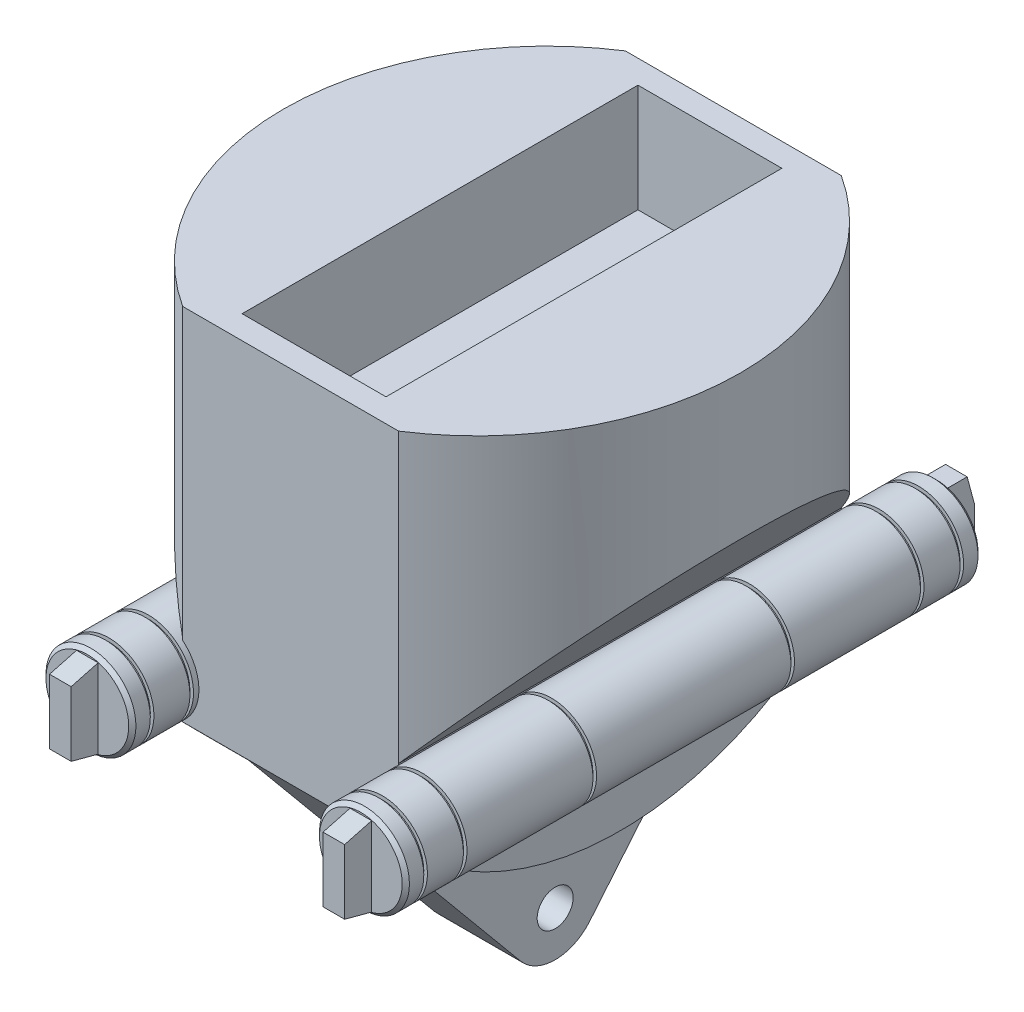
SolidWorks part; units mm, degrees
ref_plane "Front Plane" through (0, 0, 0) normal (0, 0, 1) x (1, 0, 0)
ref_plane "Top Plane" through (0, 0, 0) normal (0, 1, 0) x (1, 0, 0)
ref_plane "Right Plane" through (0, 0, 0) normal (1, 0, 0) x (0, 0, -1)
sketch "Sketch1" plane through (0, 0, 0) normal (1, 0, 0) x (0, 0, -1)
  line L1 (-61.5, 83.5) -> (61.5, 83.5)
  line L2 (-61.5, 83.5) -> (-61.5, -83.5)
  line L3 (-61.5, -83.5) -> (61.5, -83.5)
  line L4 (61.5, 83.5) -> (61.5, -83.5)
  line L5 (-61.5, 83.5) -> (61.5, -83.5) construction
  line L6 (-61.5, -83.5) -> (61.5, 83.5) construction
  point P0 (0, 0)
  dimension "D1" = 123
  dimension "D2" = 167
extrude "Boss-Extrude1" add sketch "Sketch1" along normal mid plane 127
sketch "Sketch2" plane through (0, 83.5, 0) normal (0, 1, 0) x (1, 0, 0)
  line L0 (0, 61.5) -> (0, -61.5) construction
  line L1 (63.5, 61.5) -> (-63.5, 61.5) construction
  line L2 (63.5, -61.5) -> (-63.5, -61.5) construction
  line L3 (-30, 61.5) -> (-30, -61.5) construction
  line L4 (-30, 61.5) -> (-63.5, 61.5)
  line L5 (-63.5, 61.5) -> (-63.5, -61.5)
  line L6 (-63.5, -61.5) -> (-30, -61.5)
  line L7 (63.5, -61.5) -> (30, -61.5)
  line L8 (30, 61.5) -> (63.5, 61.5)
  line L9 (63.5, 61.5) -> (63.5, -61.5)
  arc A0 (-30, 61.5) -> (-30, -61.5) centre (9.7015, 0) ccw
  arc A1 (30, 61.5) -> (30, -61.5) centre (-9.7015, 0) cw
  line M6 (-63.5, 61.5) -> (-63.5, -61.5)
  line M7 (-63.5, -61.5) -> (63.5, -61.5)
  line M8 (63.5, -61.5) -> (63.5, 61.5)
  line M9 (63.5, 61.5) -> (-63.5, 61.5)
  dimension "D2" = 73.2015
  dimension "D1" = 30
extrude "Cut-Extrude1" cut sketch "Sketch2" against normal through all contours A0 M9 M6 | A0 L5 M7 | A1 M8 M7 | A1 L9 M9 region at (-54.0203, 83.5, -46.9159) region at (-54.0203, 83.5, 46.9159) region at (54.0203, 83.5, -46.9159) region at (54.0203, 83.5, 46.9159)
sketch "Sketch3" plane through (0, 0, 61.5) normal (0, 0, 1) x (1, 0, 0)
  line L0 (0, 83.5) -> (0, -83.5) construction
  line L3 (30, 83.5) -> (-30, 83.5) construction
  line L4 (-12, -83.5) -> (-12, -43.5)
  line L5 (-12, -43.5) -> (-30, -43.5)
  line L6 (-30, -83.5) -> (-30, 83.5) construction
  line L7 (30, -83.5) -> (-30, -83.5) construction
  line L8 (-12, -83.5) -> (0, -83.5) construction
  line L9 (-30, -43.5) -> (-30, 3.5)
  line L10 (-30, 3.5) -> (-63.5, 43.5)
  line L11 (-63.5, 83.5) -> (-63.5, -83.5) construction
  line L12 (-63.5, 43.5) -> (-63.5, -83.5)
  line L13 (-63.5, -83.5) -> (-12, -83.5)
  line L14 (63.5, -83.5) -> (12, -83.5)
  line L15 (63.5, 43.5) -> (63.5, -83.5)
  line L16 (30, 3.5) -> (63.5, 43.5)
  line L17 (30, -43.5) -> (30, 3.5)
  line L18 (12, -43.5) -> (30, -43.5)
  line L19 (12, -83.5) -> (12, -43.5)
  dimension "D1" = 12
  dimension "D2" = 40
  dimension "D3" = 40
  dimension "D4" = 80
extrude "Cut-Extrude2" cut sketch "Sketch3" against normal through all
sketch "Sketch4" plane through (-30, 0, 0) normal (-1, 0, 0) x (0, 0, 1)
  line L0 (-61.5, -43.5) -> (-61.5, 3.5) construction
  line L1 (61.5, -43.5) -> (61.5, 3.5) construction
  line L2 (-61.5, -43.5) -> (61.5, -43.5) construction
  line L3 (-61.5, -16.5) -> (-61.5, -43.5)
  line L4 (-61.5, -43.5) -> (61.5, -43.5)
  line L5 (61.5, -43.5) -> (61.5, -16.5)
  arc A0 (-61.5, -16.5) -> (61.5, -16.5) centre (0, 40.0417) ccw
  point P9 (0, -43.5)
  line M1 (61.5, -43.5) -> (61.5, 3.5)
  line M3 (-61.5, 3.5) -> (-61.5, -43.5)
  line M4 (-61.5, -43.5) -> (61.5, -43.5)
  dimension "D1" = 20
extrude "Cut-Extrude3" cut sketch "Sketch4" against normal blind 18 contours A0 M3 M4 | A0 L4 M1 region at (-30, -35.6872, -46.6662) region at (-30, -35.6872, 46.6662)
mirror "Mirror1" about plane through (0, 0, 0) normal (1, 0, 0) of "Cut-Extrude3"
sketch "Sketch5" plane through (-12, 0, 0) normal (-1, 0, 0) x (0, 0, 1)
  line L0 (-61.5, -16.5) -> (-61.5, -83.5)
  line L1 (-61.5, -83.5) -> (61.5, -83.5)
  line L2 (61.5, -83.5) -> (61.5, -16.5)
  line L3 (0, -58.5) -> (0, -83.5) construction
  line L4 (-61.5, -16.5) -> (-9.617, -78.9852)
  line L5 (0, 0) -> (0, -71) construction
  line L6 (61.5, -16.5) -> (9.617, -78.9852)
  arc A0 (-9.617, -78.9852) -> (9.617, -78.9852) centre (0, -71) ccw
  circle A1 centre (0, -71) radius 5
  line M5 (61.5, -83.5) -> (61.5, -16.5)
  line M7 (-61.5, -16.5) -> (-61.5, -83.5)
  line M8 (-61.5, -83.5) -> (61.5, -83.5)
  dimension "D1" = 25
  dimension "D2" = 10
extrude "Cut-Extrude4" cut sketch "Sketch5" against normal through all contours A0 L4 M7 M8 | A0 L1 L6 M5 | A1 region at (-12, -61.2213, -42.8602) region at (-12, -61.2213, 42.8602) region at (-12, -71, 0)
sketch "Sketch6" plane through (0, 0, 0) normal (0, 0, 1) x (1, 0, 0)
  line L1 (30, 3.5) -> (30, 3.2345)
  line L2 (30, 3.5) -> (30, -16.5) construction
  line L6 (0, 83.5) -> (0, 0) construction
  line L7 (30, 83.5) -> (-30, 83.5) construction
  line L10 (-30, 3.5) -> (-30, 3.2345)
extrude "Boss-Extrude2" add sketch "Sketch6" along normal mid plane 40 separate body rebuild error yes
sketch "Sketch7" plane through (0, 0, 0) normal (0, 0, 1) x (1, 0, 0)
  circle A0 centre (38, -6.5) radius 12.5
  dimension "D1" = 25
extrude "Boss-Extrude3" add sketch "Sketch7" along normal mid plane 160
sketch "Sketch8" plane through (0, 0, 80) normal (0, 0, 1) x (1, 0, 0)
  line L1 (35, 4.5) -> (41, 4.5)
  line L2 (35, 4.5) -> (35, -17.5)
  line L3 (35, -17.5) -> (41, -17.5)
  line L4 (41, 4.5) -> (41, -17.5)
  line L5 (35, 4.5) -> (41, -17.5) construction
  line L6 (35, -17.5) -> (41, 4.5) construction
  point P0 (38, -6.5)
  dimension "D1" = 22
  dimension "D2" = 6
extrude "Boss-Extrude4" add sketch "Sketch8" along normal blind 7.5
ref_plane "Plane1" through (38, 0, 0) normal (1, 0, 0) x (0, 0, -1)
sketch "Sketch9" plane through (38, 0, 0) normal (1, 0, 0) x (0, 0, -1)
  line L0 (80, 6) -> (-80, 6) construction
  line L1 (-75, 6) -> (-74, 6)
  line L2 (-75, 6) -> (-75, 5)
  line L3 (-75, 5) -> (-74, 5)
  line L4 (-74, 6) -> (-74, 5)
  line L5 (-80, 6) -> (80, 6) construction
  line L6 (-64, 6) -> (-63, 6)
  line L7 (-64, 6) -> (-64, 5)
  line L8 (-64, 5) -> (-63, 5)
  line L9 (-63, 6) -> (-63, 5)
  line L10 (0, 6) -> (0, 0) construction
  line L11 (28, 5) -> (27, 5)
  line L12 (-28, 6) -> (-27, 6)
  line L13 (-28, 6) -> (-28, 5)
  line L14 (-28, 5) -> (-27, 5)
  line L15 (-27, 6) -> (-27, 5)
  line L16 (27, 6) -> (27, 5)
  line L17 (28, 6) -> (27, 6)
  line L18 (28, 6) -> (28, 5)
  line L19 (63, 6) -> (63, 5)
  line L20 (64, 6) -> (63, 6)
  line L21 (64, 5) -> (63, 5)
  line L22 (64, 6) -> (64, 5)
  line L23 (74, 6) -> (74, 5)
  line L24 (75, 6) -> (74, 6)
  line L25 (75, 6) -> (75, 5)
  line L26 (75, 5) -> (74, 5)
  line L27 (-80, -6.5) -> (80, -6.5) construction
  line L28 (-80, -17.5) -> (-80, 4.5) construction
  line L29 (80, -19) -> (80, 6) construction
  dimension "D1" = 1
  dimension "D2" = 10
  dimension "D3" = 5
  dimension "D4" = 35
revolve "Cut-Revolve1" cut sketch "Sketch9" angle 360 about L27
mirror "Mirror2" about plane through (0, 0, 0) normal (0, 0, 1) of "Boss-Extrude4"
chamfer "Chamfer1" distance 1 angle 45 2 edges at (50.5, -6.5, -80) (50.5, -6.5, 80)
chamfer "Chamfer2" distance 7.5 angle 15 4 edges at (38, -17.5, -87.5) (38, 4.5, -87.5) (38, -17.5, 87.5) (38, 4.5, 87.5) first distance on face at (38, -6.5, -87.5) first distance on face at (38, -17.5, 83.75) first distance on face at (38, 4.5, 83.75)
mirror "Mirror3" about plane through (0, 0, 0) normal (1, 0, 0) of "Cut-Revolve1", "Chamfer2", "Chamfer1", "Mirror2", "Boss-Extrude3", "Boss-Extrude4"
sketch "Sketch10" plane through (0, 83.5, 0) normal (0, 1, 0) x (1, 0, 0)
  line L1 (-20, 55) -> (20, 55)
  line L2 (-20, 55) -> (-20, -55)
  line L3 (-20, -55) -> (20, -55)
  line L4 (20, 55) -> (20, -55)
  line L5 (-20, 55) -> (20, -55) construction
  line L6 (-20, -55) -> (20, 55) construction
  point P0 (0, 0)
  dimension "D1" = 40
  dimension "D2" = 110
extrude "Boss-Extrude5" add sketch "Sketch10" along normal blind 30
scale "Scale1" bodies to scale 108 114 scale about centroid uniform scaling yes scale factor 0.333333
sketch "Sketch11" plane through (0, 58.6071, 0) normal (0, 1, 0) x (1, 0, 0)
  line L1 (-6.6667, 18.3332) -> (6.6667, 18.3332)
  line L2 (-6.6667, 18.3332) -> (-6.6667, -18.3335)
  line L3 (-6.6667, -18.3335) -> (6.6667, -18.3335)
  line L4 (6.6667, 18.3332) -> (6.6667, -18.3335)
extrude "Cut-Extrude5" cut sketch "Sketch11" against normal blind 20
